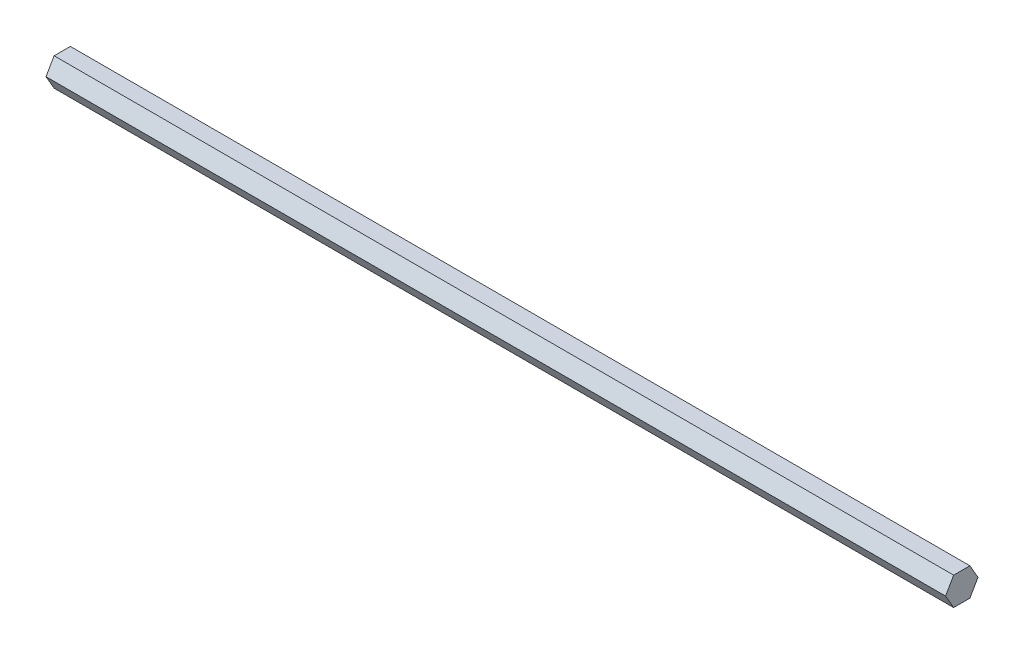
SolidWorks part; units mm, degrees
material "7075-T6 (SN)"
ref_plane "Front Plane" through (0, 0, 0) normal (0, 0, 1) x (1, 0, 0)
ref_plane "Top Plane" through (0, 0, 0) normal (0, 1, 0) x (1, 0, 0)
ref_plane "Right Plane" through (0, 0, 0) normal (1, 0, 0) x (0, 0, -1)
sketch "Sketch1" plane through (0, 0, 0) normal (1, 0, 0) x (0, 0, -1)
  line L1 (7.3323, 0) -> (3.6662, 6.35)
  line L2 (3.6662, 6.35) -> (-3.6662, 6.35)
  line L3 (-3.6662, 6.35) -> (-7.3323, 0)
  line L4 (-7.3323, 0) -> (-3.6662, -6.35)
  line L5 (-3.6662, -6.35) -> (3.6662, -6.35)
  line L6 (3.6662, -6.35) -> (7.3323, 0)
  circle A0 centre (0, 0) radius 6.35 construction
  dimension "D1" = 12.7
extrude "Boss-Extrude1" add sketch "Sketch1" along normal mid plane 406.4
ref_axis "Axis1" through (-230.505, 0, 0) along (1, 0, 0)
